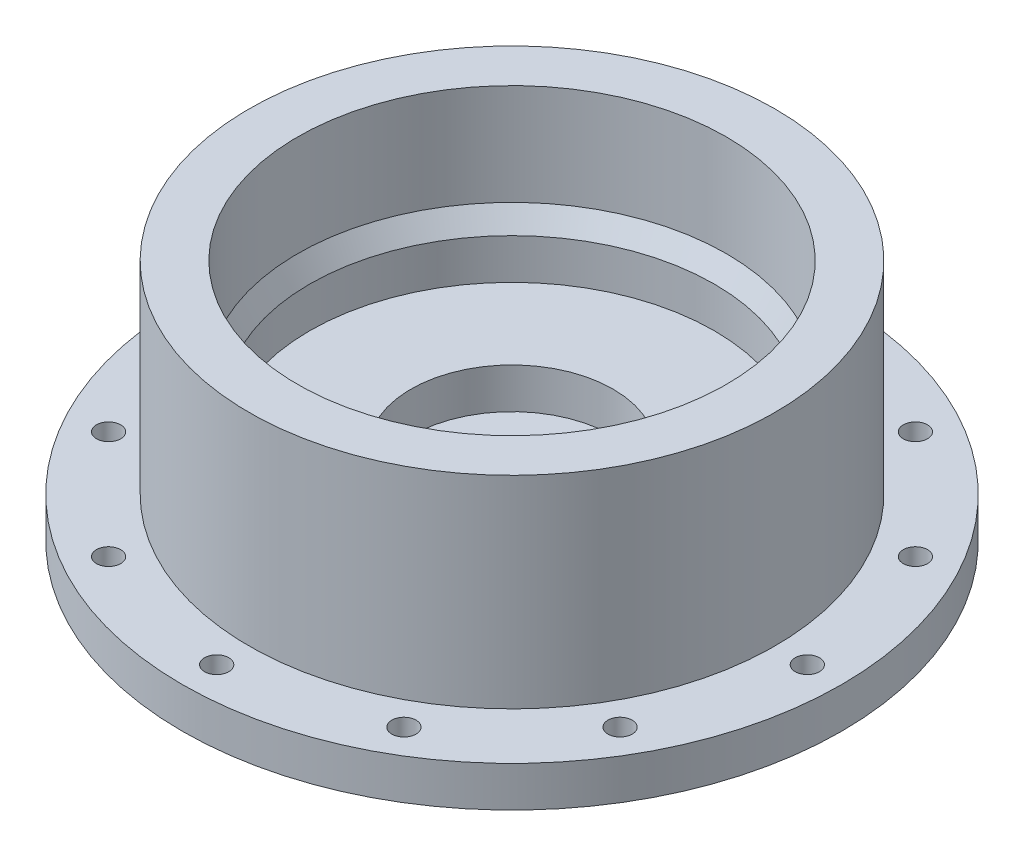
SolidWorks part; units mm, degrees
ref_plane "Front Plane" through (0, 0, 0) normal (0, 0, 1) x (1, 0, 0)
ref_plane "Top Plane" through (0, 0, 0) normal (0, 1, 0) x (1, 0, 0)
ref_plane "Right Plane" through (0, 0, 0) normal (1, 0, 0) x (0, 0, -1)
sketch "Sketch1" plane through (0, 0, 0) normal (1, 0, 0) x (0, 0, -1)
  line L0 (0, 0) -> (25, 0) construction
  line L1 (25, 0) -> (25, -10)
  line L2 (25, 0) -> (50, 0)
  line L3 (50, 0) -> (50, 10)
  line L5 (65, 40) -> (65, -10)
  line L6 (65, -10) -> (25, -10) construction
  line L7 (0, 0) -> (0, 10) construction
  line L8 (25, -10) -> (0, -10)
  line L9 (0, -10) -> (0, -20)
  line L10 (0, -20) -> (65, -20)
  line L11 (65, -20) -> (65, -10)
  line L12 (50, 10) -> (53, 15)
  line L13 (53, 15) -> (53, 40)
  line L14 (53, 40) -> (65, 40)
  point P13 (59, 40)
  point P15 (50, 15.1156)
  dimension "D1" = 25
  dimension "D2" = 10
  dimension "D3" = 50
  dimension "D4" = 40
  dimension "D5" = 10
  dimension "D6" = 40
  dimension "D7" = 10
  dimension "D8" = 3
  dimension "D9" = 5
  dimension "D10" = 10
revolve "Revolve1" add sketch "Sketch1" angle 360 about L7
sketch "Sketch2" plane through (0, 0, 0) normal (0, 1, 0) x (1, 0, 0)
  line L3 (0, 0) -> (0, 73) construction
  circle A4 centre (0, 73) radius 3
  circle A8 centre (0, 0) radius 81.5
  circle A9 centre (36.5, 63.2199) radius 3
  circle A10 centre (63.2199, 36.5) radius 3
  circle A11 centre (73, 0) radius 3
  circle A12 centre (63.2199, -36.5) radius 3
  circle A13 centre (36.5, -63.2199) radius 3
  circle A14 centre (0, -73) radius 3
  circle A15 centre (-36.5, -63.2199) radius 3
  circle A16 centre (-63.2199, -36.5) radius 3
  circle A17 centre (-73, 0) radius 3
  circle A18 centre (-63.2199, 36.5) radius 3
  circle A19 centre (-36.5, 63.2199) radius 3
  point P29 (0, 0)
  dimension "D1" = 6
  dimension "D2" = 163
  dimension "D3" = 73
  dimension "D4" = 12
extrude "Boss-Extrude1" add sketch "Sketch2" along normal blind 10 from surface contours A4 region at (0, 0, 0) starting at face at (0, -20, -65)
